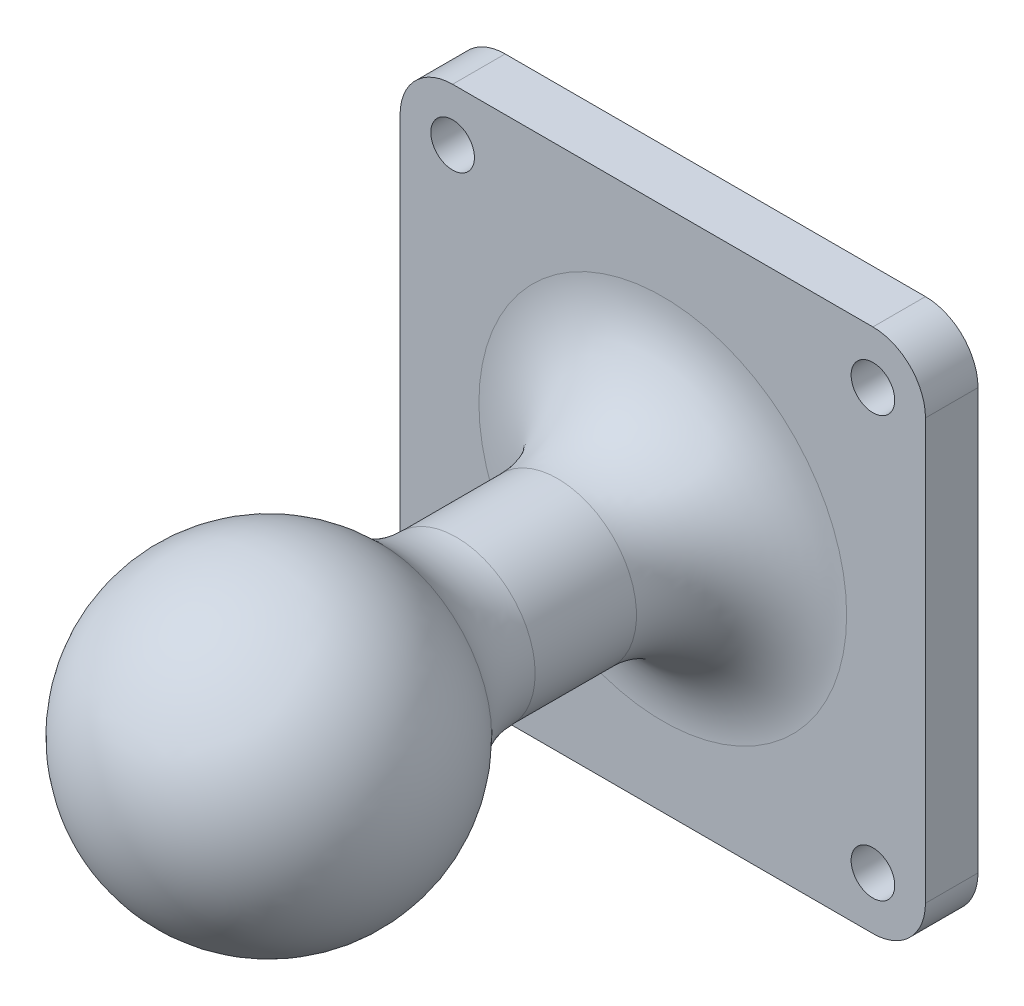
SolidWorks part; units mm, degrees
ref_plane "Alzado" through (0, 0, 0) normal (0, 0, 1) x (1, 0, 0)
ref_plane "Planta" through (0, 0, 0) normal (0, 1, 0) x (1, 0, 0)
ref_plane "Vista lateral" through (0, 0, 0) normal (1, 0, 0) x (0, 0, -1)
sketch "Croquis1" plane through (0, 0, 0) normal (0, 0, 1) x (1, 0, 0)
  line L1 (-25, -25) -> (25, -25)
  line L2 (-25, -25) -> (-25, 25)
  line L3 (-25, 25) -> (25, 25)
  line L4 (25, -25) -> (25, 25)
  line L5 (-25, -25) -> (25, 25) construction
  line L6 (-25, 25) -> (25, -25) construction
  point P0 (0, 0)
  dimension "D1" = 50
  dimension "D2" = 50
extrude "Saliente-Extruir1" add sketch "Croquis1" along normal blind 5
sketch "Croquis2" plane through (0, 0, 5) normal (0, 0, 1) x (1, 0, 0)
  circle A0 centre (0, 0) radius 7.5
  dimension "D1" = 15
ref_plane "Plano1" through (0, 0, 42.5) normal (0, 0, 1) x (1, 0, 0)
sketch "Croquis3" plane through (0, 0, 42.5) normal (0, 0, 1) x (1, 0, 0)
  line L0 (0, 15) -> (0, -15) construction
  line L1 (0, 15) -> (0, -15)
  arc A0 (0, -15) -> (0, 15) centre (0, 0) ccw
  dimension "D1" = 30
revolve "Revolución1" add sketch "Croquis3" angle 360 about L0
extrude "Saliente-Extruir2" add sketch "Croquis2" along normal up to surface (24.5096 mm away) contours A0
sketch "Croquis4" plane through (0, 0, 5) normal (0, 0, 1) x (1, 0, 0)
  line L0 (0, 25) -> (0, 0) construction
  line L1 (25, 25) -> (-25, 25) construction
  line L2 (0, 0) -> (25, 0) construction
  line L3 (25, -25) -> (25, 25) construction
  line L4 (-25, 25) -> (-25, -25) construction
  circle A0 centre (-20, 20) radius 1.5
  circle A1 centre (20, 20) radius 1.5
  circle A2 centre (20, -20) radius 1.5
  circle A3 centre (-20, -20) radius 1.5
  dimension "D1" = 3
  dimension "D3" = 5
  dimension "D2" = 5
extrude "Cortar-Extruir1" cut sketch "Croquis4" against normal blind 5
fillet "Redondeo1" radius 5 4 edges at (25, -25, 2.5) (25, 25, 2.5) (-25, 25, 2.5) (-25, -25, 2.5)
sketch "Sketch1" plane through (0, 0, 5) normal (0, 0, 1) x (1, 0, 0)
  circle A1 centre (-20, 20) radius 2.075
  circle A2 centre (20, 20) radius 2.075
  circle A3 centre (20, -20) radius 2.075
  circle A4 centre (-20, -20) radius 2.075
  dimension "D1" = 4.15
  dimension "D2" = 4.15
  dimension "D3" = 4.15
  dimension "D4" = 4.15
  dimension "D5" = 40
  dimension "D6" = 40
extrude "Cut-Extrude1" cut sketch "Sketch1" against normal blind 10
fillet "Redondeo2" radius 10 2 edges at (7.5, 0, 29.5096) (7.5, 0, 5)
